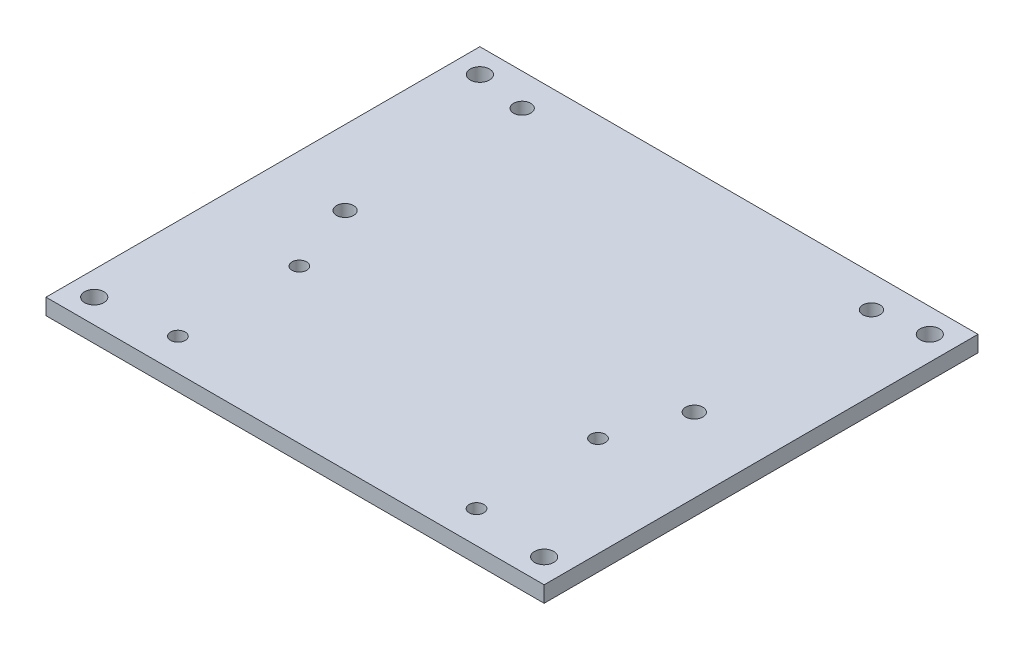
SolidWorks part; units mm, degrees
material "Pine"
ref_plane "Front Plane" through (0, 0, 0) normal (0, 0, 1) x (1, 0, 0)
ref_plane "Top Plane" through (0, 0, 0) normal (0, 1, 0) x (1, 0, 0)
ref_plane "Right Plane" through (0, 0, 0) normal (1, 0, 0) x (0, 0, -1)
sketch "Sketch1" plane through (0, 0, 0) normal (0, 1, 0) x (1, 0, 0)
  line L0 (-49.2125, 42.8625) -> (49.2125, 42.8625)
  line L1 (-44.45, -38.1) -> (44.45, -38.1) construction
  line L2 (-44.45, -38.1) -> (-44.45, 38.1) construction
  line L3 (-44.45, 38.1) -> (44.45, 38.1) construction
  line L4 (44.45, -38.1) -> (44.45, 38.1) construction
  line L5 (-44.45, -38.1) -> (44.45, 38.1) construction
  line L6 (-44.45, 38.1) -> (44.45, -38.1) construction
  line L7 (49.2125, -42.8625) -> (49.2125, 42.8625)
  line L8 (-49.2125, -42.8625) -> (49.2125, -42.8625)
  line L9 (-49.2125, -42.8625) -> (-49.2125, 42.8625)
  point P0 (0, 0)
  dimension "D1" = 88.9
  dimension "D2" = 76.2
  dimension "D3" = 4.7625
extrude "Boss-Extrude1" add sketch "Sketch1" along normal blind 3.175
hole_wizard "#6 Clearance Hole1" positions "3DSketch1" profile "Sketch2" hole size "#6" standard "ANSI Inch" end condition through all
sketch3d "3DSketch1"
  point P0 (-44.45, 0, 38.1)
  point P3 (44.45, 0, 38.1)
  point P6 (-44.45, 0, -38.1)
  point P9 (44.45, 0, -38.1)
sketch "Sketch2" plane through (-44.45, 0, 38.1) normal (1, 0, 0) x (0, 0, -1)
  line L0 (0, 0) -> (0, 3.175)
  line L1 (0, 3.175) -> (1.8986, 3.175)
  line L2 (1.8986, 3.175) -> (1.8986, 0)
  line L5 (1.8986, 0) -> (0, 0)
  line L11 (0, -6.35) -> (0, 107.95) construction
  dimension "Thru Hole Dia." = 3.7973
  dimension "Thru Hole Depth" = 3.175
sketch "Sketch3" plane through (0, 3.175, 0) normal (0, 1, 0) x (1, 0, 0)
  line L0 (0, 19.0125) -> (0, -24.5125) construction
  line L1 (-34.5, 36.5125) -> (34.5, 36.5125) construction
  line L2 (-34.5, 36.5125) -> (-34.5, 1.5125) construction
  line L3 (-34.5, 1.5125) -> (34.5, 1.5125) construction
  line L4 (34.5, 36.5125) -> (34.5, 1.5125) construction
  line L5 (-34.5, 36.5125) -> (34.5, 1.5125) construction
  line L6 (-34.5, 1.5125) -> (34.5, 36.5125) construction
  line L7 (-29.5, -36.5125) -> (29.5, -36.5125) construction
  line L8 (-29.5, -36.5125) -> (-29.5, -12.5125) construction
  line L9 (-29.5, -12.5125) -> (29.5, -12.5125) construction
  line L10 (29.5, -36.5125) -> (29.5, -12.5125) construction
  line L11 (-29.5, -36.5125) -> (29.5, -12.5125) construction
  line L12 (-29.5, -12.5125) -> (29.5, -36.5125) construction
  line L13 (-49.2125, -42.8625) -> (49.2125, -42.8625) construction
  line L14 (49.2125, 42.8625) -> (-49.2125, 42.8625) construction
  point P0 (0, 19.0125)
  point P5 (0, -24.5125)
  dimension "D1" = 69
  dimension "D2" = 35
  dimension "D3" = 59
  dimension "D4" = 24
  dimension "D5" = 6.35
  dimension "D6" = 6.35
hole_wizard "M2.5 Clearance Hole1" positions "3DSketch2" profile "Sketch4" hole size "M2.5" standard "ANSI Metric" end condition through all
sketch3d "3DSketch2"
  point P0 (-29.5, 3.175, 36.5125)
  point P3 (-29.5, 3.175, 12.5125)
  point P6 (29.5, 3.175, 12.5125)
  point P9 (29.5, 3.175, 36.5125)
sketch "Sketch4" plane through (-29.5, 3.175, 36.5125) normal (1, 0, 0) x (0, 0, 1)
  line L0 (0, 0) -> (0, 3.175)
  line L1 (0, 3.175) -> (1.45, 3.175)
  line L2 (1.45, 3.175) -> (1.45, 0)
  line L5 (1.45, 0) -> (0, 0)
  line L11 (0, -6.35) -> (0, 107.95) construction
  dimension "Thru Hole Dia." = 2.9
  dimension "Thru Hole Depth" = 3.175
hole_wizard "M3 Clearance Hole1" positions "3DSketch3" profile "Sketch5" hole size "M3" standard "ANSI Metric" end condition through all
sketch3d "3DSketch3"
  point P0 (-34.5, 3.175, -36.5125)
  point P3 (34.5, 3.175, -36.5125)
  point P6 (34.5, 3.175, -1.5125)
  point P9 (-34.5, 3.175, -1.5125)
sketch "Sketch5" plane through (-34.5, 3.175, -36.5125) normal (1, 0, 0) x (0, 0, 1)
  line L0 (0, 0) -> (0, 3.175)
  line L1 (0, 3.175) -> (1.7, 3.175)
  line L2 (1.7, 3.175) -> (1.7, 0)
  line L5 (1.7, 0) -> (0, 0)
  line L11 (0, -6.35) -> (0, 107.95) construction
  dimension "Thru Hole Dia." = 3.4
  dimension "Thru Hole Depth" = 3.175
equation "\"D5@Sketch3\"=\"D6@Sketch3\""
